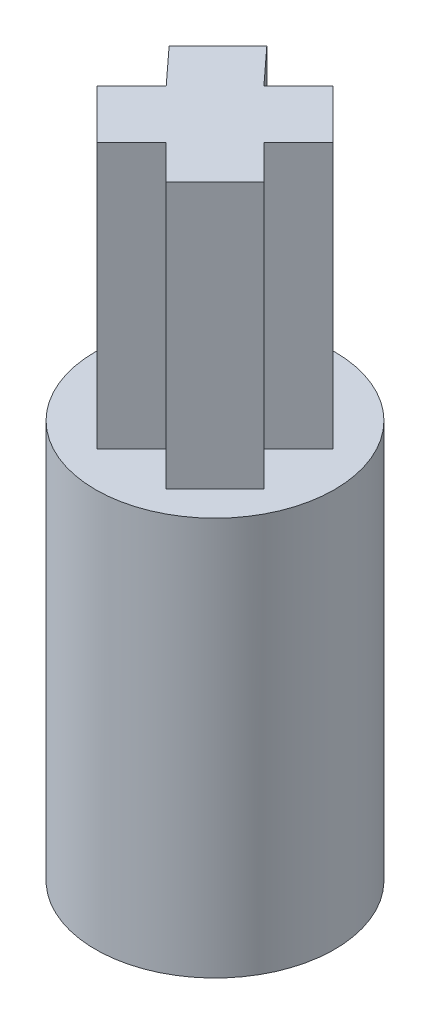
SolidWorks part; units mm, degrees
ref_plane "Front Plane" through (0, 0, 0) normal (0, 0, 1) x (1, 0, 0)
ref_plane "Top Plane" through (0, 0, 0) normal (0, 1, 0) x (1, 0, 0)
ref_plane "Right Plane" through (0, 0, 0) normal (1, 0, 0) x (0, 0, -1)
sketch "Sketch1" plane through (0, 0, 0) normal (0, 1, 0) x (1, 0, 0)
  circle A2 centre (0, 0) radius 5.715
  dimension "D3" = 11.43
extrude "Boss-Extrude1" add sketch "Sketch1" along normal blind 6.35
sketch "Sketch3" plane through (0, 0, 0) normal (0, -1, 0) x (-1, 0, 0)
  circle A0 centre (0, 0) radius 5.715
extrude "Boss-Extrude2" add sketch "Sketch3" along normal blind 12.7
sketch "Sketch4" plane through (0, -12.7, 0) normal (0, -1, 0) x (1, 0, 0)
  line L0 (0, 2.54) -> (-1.7961, 4.3361)
  line L1 (-2.54, -2.54) -> (2.54, -2.54) construction
  line L2 (-2.54, -2.54) -> (-2.54, 2.54) construction
  line L3 (-2.54, 2.54) -> (2.54, 2.54) construction
  line L4 (2.54, -2.54) -> (2.54, 2.54) construction
  line L5 (-2.54, -2.54) -> (2.54, 2.54) construction
  line L6 (-2.54, 2.54) -> (2.54, -2.54) construction
  line L7 (-2.54, 0) -> (-4.3361, 1.7961)
  line L8 (-4.3361, 1.7961) -> (-1.7961, 4.3361)
  line L9 (2.54, 0) -> (4.3361, -1.7961)
  line L10 (0, -2.54) -> (1.7961, -4.3361)
  line L11 (1.7961, -4.3361) -> (4.3361, -1.7961)
  line L12 (-2.54, 0) -> (-4.3361, -1.7961)
  line L13 (0, -2.54) -> (-1.7961, -4.3361)
  line L14 (-4.3361, -1.7961) -> (-1.7961, -4.3361)
  line L15 (2.54, 0) -> (4.3361, 1.7961)
  line L16 (1.7961, 4.3361) -> (4.3361, 1.7961)
  line L17 (0, 2.54) -> (1.7961, 4.3361)
  point P0 (0, 0)
  dimension "D1" = 2.54
  dimension "D2" = 5.08
  dimension "D3" = 5.08
  dimension "D4" = 8.6721
  dimension "D5" = 3.5921
  dimension "D6" = 3.5921
  dimension "D7" = 3.5921
  dimension "D8" = 3.5921
  dimension "D9" = 8.6721
  dimension "D10" = 0
  dimension "D11" = 3.5921
  dimension "D12" = 5.08
  dimension "D13" = 2.54
  dimension "D14" = 2.54
  dimension "D15" = 2.54
  dimension "D16" = 2.54
  dimension "D17" = 2.54
  dimension "D18" = 2.54
  dimension "D19" = 2.54
  dimension "D20" = 2.54
extrude "Cut-Extrude1" cut sketch "Sketch4" against normal blind 12.7
sketch "Sketch5" plane through (0, 6.35, 0) normal (0, 1, 0) x (1, 0, 0)
  line L0 (0, 2.5419) -> (-1.7372, 4.3949) construction
  line L1 (-2.54, -2.54) -> (2.54, -2.54) construction
  line L2 (-2.54, -2.54) -> (-2.54, 2.54) construction
  line L3 (-2.54, 2.54) -> (2.54, 2.54) construction
  line L4 (2.54, -2.54) -> (2.54, 2.54) construction
  line L5 (-2.54, -2.54) -> (2.54, 2.54) construction
  line L6 (-2.54, 2.54) -> (2.54, -2.54) construction
  line L7 (-2.54, 0.0019) -> (-4.2772, 1.8549) construction
  line L8 (-4.2772, 1.8549) -> (-1.7372, 4.3949) construction
  line L9 (2.54, 0) -> (4.3361, -1.7961) construction
  line L10 (0, -2.54) -> (1.7961, -4.3361) construction
  line L11 (1.7961, -4.3361) -> (4.3361, -1.7961) construction
  line L12 (-2.54, 0.0019) -> (-4.3358, -1.7945) construction
  line L13 (0, -2.54) -> (-1.7967, -4.3354) construction
  line L14 (-4.3358, -1.7945) -> (-1.7967, -4.3354) construction
  line L15 (2.54, 0) -> (4.3372, 1.7949) construction
  line L16 (1.7981, 4.3359) -> (4.3372, 1.7949) construction
  line L17 (0, 2.5419) -> (1.7981, 4.3359) construction
  line L18 (0, 2.3397) -> (1.6556, 3.9889)
  line L19 (-3.9887, -1.6499) -> (-1.6534, -3.9881)
  line L20 (-3.9181, 1.7234) -> (-1.5813, 4.0602)
  line L21 (0, -2.3368) -> (1.6524, -3.9892)
  line L22 (1.6524, -3.9892) -> (3.9892, -1.6524)
  line L23 (-2.3368, 0.0029) -> (-3.9887, -1.6499)
  line L24 (0, -2.3368) -> (-1.6534, -3.9881)
  line L25 (2.3368, 0) -> (3.9909, 1.6506)
  line L26 (0, 2.3397) -> (-1.5813, 4.0602)
  line L27 (-2.3368, 0.0029) -> (-3.9181, 1.7234)
  line L28 (1.6556, 3.9889) -> (3.9909, 1.6506)
  line L29 (2.3368, 0) -> (3.9892, -1.6524)
  point P0 (0, 0)
  dimension "D1" = 2.54
  dimension "D2" = 5.08
  dimension "D3" = 5.08
  dimension "D4" = 8.6721
  dimension "D5" = 3.5921
  dimension "D6" = 3.5921
  dimension "D7" = 3.5921
  dimension "D8" = 3.5921
  dimension "D9" = 8.6721
  dimension "D10" = 0
  dimension "D11" = 3.5921
  dimension "D12" = 5.08
  dimension "D13" = 2.54
  dimension "D14" = 2.54
  dimension "D15" = 2.54
  dimension "D16" = 2.54
  dimension "D17" = 2.54
  dimension "D18" = 2.54
  dimension "D19" = 2.54
  dimension "D20" = 2.54
extrude "Boss-Extrude3" add sketch "Sketch5" along normal blind 12.7
